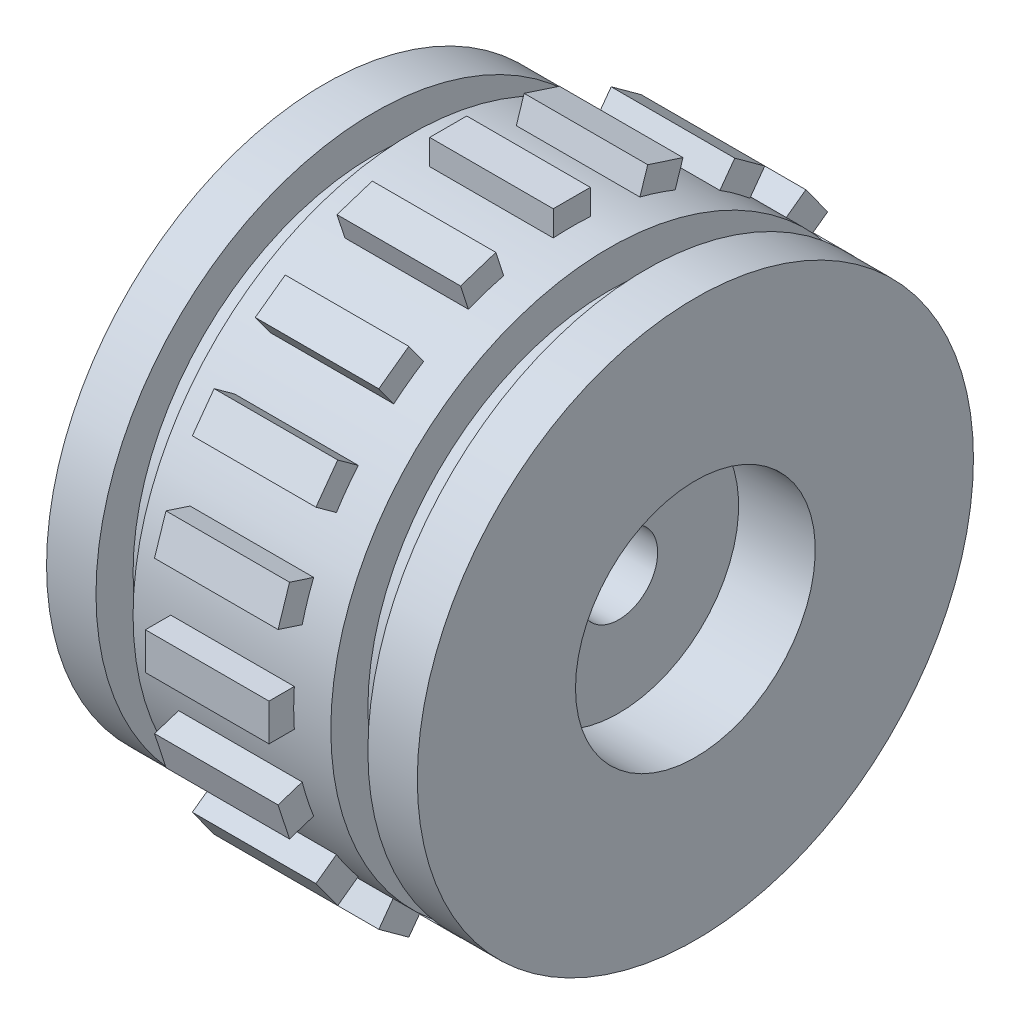
SolidWorks part; units mm, degrees
material "ABS"
ref_plane "Спереди" through (0, 0, 0) normal (0, 0, 1) x (1, 0, 0)
ref_plane "Сверху" through (0, 0, 0) normal (0, 1, 0) x (1, 0, 0)
ref_plane "Справа" through (0, 0, 0) normal (1, 0, 0) x (0, 0, -1)
sketch "Эскиз4" plane through (0, 0, 0) normal (0, 0, 1) x (1, 0, 0)
  line L0 (-30, 0) -> (0, 0) construction
  line L1 (-30, 22.5) -> (-30, 18.5)
  line L2 (-30, 18.5) -> (-19, 18.5)
  line L4 (-19, 18.5) -> (-19, 5.15)
  line L5 (-13, 3.15) -> (0, 3.15)
  line L9 (0, 22.5) -> (-30, 22.5)
  line L11 (-6.2, 3.15) -> (-6.2, 9.7)
  line L15 (0, 22.5) -> (0, 3.15)
  line L17 (-19, 5.15) -> (-13, 5.15)
  line L18 (-13, 5.15) -> (-13, 3.15)
  line L19 (-6.2, 9.7) -> (0, 9.7)
  dimension "D2" = 6
  dimension "D3" = 6.3
  dimension "D4" = 6.2
  dimension "D5" = 45
  dimension "D6" = 10.3
  dimension "D7" = 19.4
  dimension "D8" = 4
  dimension "D9" = 30
  dimension "D12" = 11
revolve "Повернуть1" add sketch "Эскиз4" angle 360 about L0 region at (-11.8449, 14.7794, 0)
chamfer "Фаска2" distance 2 angle 45 2 edges at (-30, 0, 18.5) (-19, 0, 18.5)
sketch "Эскиз6" plane through (0, 0, 0) normal (0, 0, 1) x (1, 0, 0)
  line L0 (-30, 18.5) -> (-30, 23.5)
  line L1 (-30, 22.5) -> (-30, -22.5) construction
  line L2 (-30, 23.5) -> (-26, 23.5)
  line L3 (-26, 23.5) -> (-26, 19.5)
  line L4 (-26, 19.5) -> (-23, 19.5)
  line L5 (-23, 19.5) -> (-23, 23.5)
  line L6 (-23, 23.5) -> (-7, 23.5)
  line L7 (-7, 23.5) -> (-7, 19.5)
  line L8 (-7, 19.5) -> (-4, 19.5)
  line L9 (-4, 19.5) -> (-4, 23.5)
  line L10 (-4, 23.5) -> (0, 23.5)
  line L11 (0, 23.5) -> (0, 18.5)
  line L12 (0, -22.5) -> (0, 22.5) construction
  line L13 (0, 18.5) -> (-30, 18.5)
  line L14 (0, 22.5) -> (-30, 22.5) construction
  line L15 (-15, 25.3568) -> (-15, 13.0667) construction
  line L16 (-26, 23.5) -> (-23, 23.5)
  line L17 (-7, 23.5) -> (-4, 23.5)
  dimension "D1" = 4
  dimension "D2" = 5
  dimension "D3" = 1
  dimension "D4" = 4
  dimension "D5" = 3
revolve "Вырез-Повернуть2" cut sketch "Эскиз6" angle 360 about L0 region at (-24.5, 21.5, 0) region at (-5.5, 21.5, 0)
sketch "Эскиз7" plane through (0, 0, 0) normal (0, 0, 1) x (1, 0, 0)
  line L0 (-15, 26.6765) -> (-15, 11.8247) construction
  line L1 (-20, 24.5) -> (-10, 24.5)
  line L2 (-20, 24.5) -> (-20, 21.0633)
  line L3 (-20, 21.0633) -> (-10, 21.0633)
  line L4 (-10, 24.5) -> (-10, 21.0633)
  line L5 (-30, 22.5) -> (-30, -22.5) construction
  line L6 (0, -22.5) -> (0, 22.5) construction
  line L7 (-7, 22.5) -> (-23, 22.5) construction
  dimension "D1" = 10
  dimension "D2" = 2
extrude "Бобышка-Вытянуть1" add sketch "Эскиз7" along normal mid plane 3
pattern_circular "Круговой массив1" count 20 over 360 about axis through (-30, 0, 0) along (-1, 0, 0) of "Бобышка-Вытянуть1"
